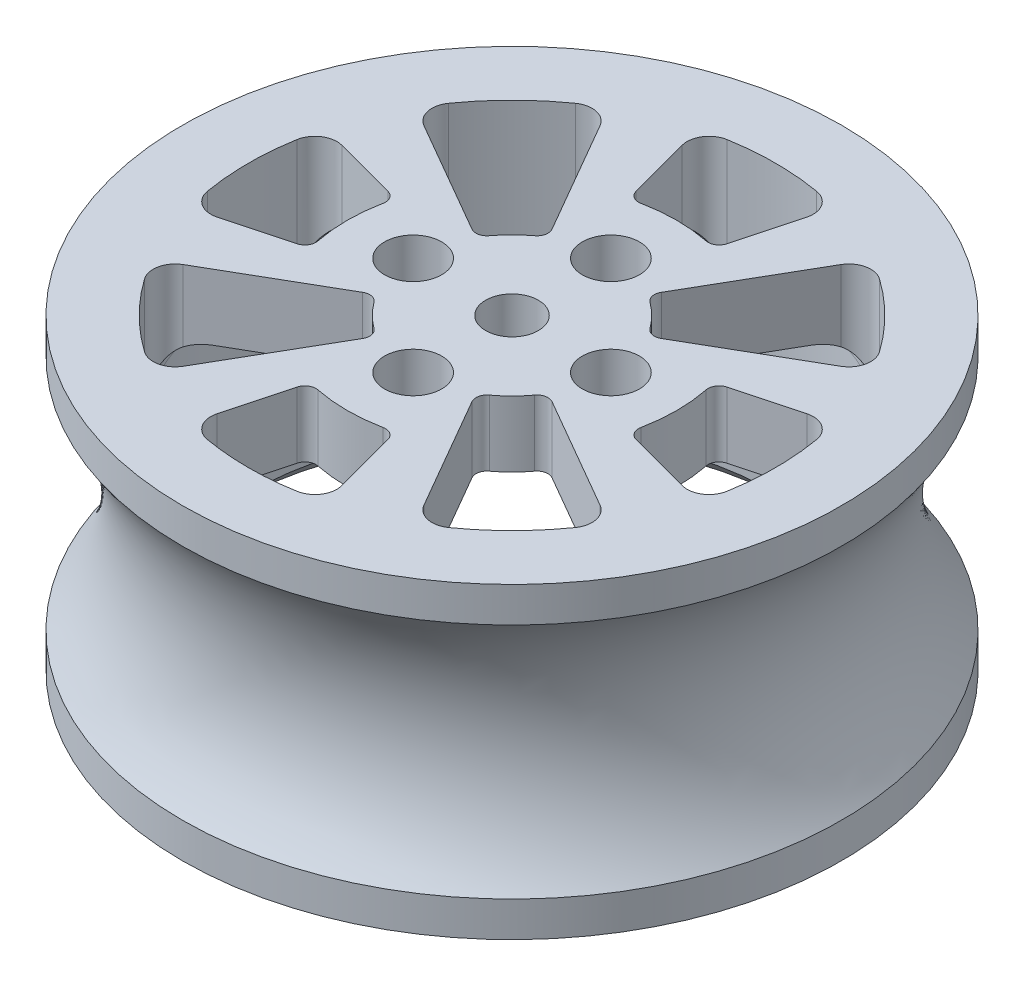
SolidWorks part; units mm, degrees
ref_plane "Front Plane" through (0, 0, 0) normal (0, 0, 1) x (1, 0, 0)
ref_plane "Top Plane" through (0, 0, 0) normal (0, 1, 0) x (1, 0, 0)
ref_plane "Right Plane" through (0, 0, 0) normal (1, 0, 0) x (0, 0, -1)
sketch "Sketch1" plane through (0, 0, 0) normal (0, 0, 1) x (1, 0, 0)
  line L0 (-0.1385, 3.875) -> (8.6615, 3.875)
  line L1 (11.8615, -0.125) -> (11.8615, 6.875) construction
  line L2 (13.6615, 6.875) -> (13.6615, 5.275)
  line L3 (-0.1385, 6.875) -> (-0.1385, 3.875)
  line L4 (10.6615, 1.875) -> (10.6615, -7.125)
  line L5 (-1.3385, 6.875) -> (-1.3385, -7.125) construction
  line L6 (13.6615, -5.525) -> (13.6615, -7.125)
  line L7 (13.6615, 6.875) -> (-0.1385, 6.875)
  line L10 (13.6615, -7.125) -> (10.6615, -7.125)
  arc A0 (13.6615, 5.275) -> (11.8615, -0.125) centre (20.8615, -0.125) ccw
  arc A1 (8.6615, 3.875) -> (10.6615, 1.875) centre (8.6615, 1.875) cw
  arc A3 (11.8615, -0.125) -> (13.6615, -5.525) centre (20.8615, -0.125) ccw
  dimension "D3" = 13.2
  dimension "D2" = 9
  dimension "D8" = 2
  dimension "D10" = 12
  dimension "D4" = 1.2
  dimension "D5" = 15
  dimension "D6" = 14
  dimension "D7" = 3
  dimension "D9" = 4
  dimension "D11" = 3.875
  dimension "D12" = 1.3385
revolve "Revolve1" add sketch "Sketch1" angle 360 about L5
hole_wizard "M2 Clearance Hole1" positions "Sketch3" profile "Sketch2" hole size "M2" standard "DIN" end condition up to next
sketch "Sketch3" plane through (0, 6.875, 0) normal (0, 1, 0) x (1, 0, 0)
  circle A4 centre (-1.3385, 0) radius 1.2 construction
  point P0 (-5.8385, 0)
  point P2 (-1.3385, 4.5)
  point P4 (3.1615, 0)
  point P6 (-1.3385, -4.5)
  dimension "D5" = 4.5
  dimension "D1" = 9
  dimension "D2" = 9
  dimension "D3" = 4.5
  dimension "D4" = 4.5
sketch "Sketch2" plane through (-5.8385, 6.875, 0) normal (1, 0, 0) x (0, 0, 1)
  line L0 (0, 0) -> (0, 3)
  line L1 (0, 3) -> (1.3, 3)
  line L2 (1.3, 3) -> (1.3, 0)
  line L5 (1.3, 0) -> (0, 0)
  line L11 (0, -6.35) -> (0, 107.95) construction
  dimension "Thru Hole Dia." = 2.6
  dimension "Thru Hole Depth" = 3
sketch "Sketch5" plane through (0, 6.875, 0) normal (0, 1, 0) x (1, 0, 0)
  line L0 (1.149, -4.3084) -> (4.1388, -9.4868)
  line L1 (2.97, -2.4875) -> (8.1484, -5.4772)
  line L2 (-1.3385, 0) -> (-9.8237, 8.4853) construction
  line L3 (-1.3385, 0) -> (-9.8237, -8.4853) construction
  line L4 (-5.6469, -2.4875) -> (-10.8253, -5.4772)
  line L5 (-3.8259, -4.3084) -> (-6.8157, -9.4868)
  line L6 (-3.8259, 4.3084) -> (-6.8157, 9.4868)
  line L7 (-5.6469, 2.4875) -> (-10.8253, 5.4772)
  line L8 (-1.3385, 12) -> (-1.3385, -12) construction
  line L9 (2.97, 2.4875) -> (8.1484, 5.4772)
  line L10 (1.149, 4.3084) -> (4.1388, 9.4868)
  line L11 (-4.1737, -10.5812) -> (-3.405, -7.7123)
  line L12 (-9.0508, -2.0665) -> (-11.9197, -2.8352)
  line L13 (-11.9197, 2.8352) -> (-9.0508, 2.0665)
  line L14 (-4.1737, 10.5812) -> (-3.405, 7.7123)
  line L15 (-13.3385, 0) -> (10.6615, 0) construction
  line L16 (-1.3385, 0) -> (-5.6469, 2.4875) construction
  line L17 (-3.8259, 4.3084) -> (-1.3385, 0) construction
  line L18 (-8.5829, -1.9411) -> (-1.3385, 0) construction
  line L19 (-1.3385, 0) -> (-8.5829, 1.9411) construction
  line L20 (-5.6469, -2.4875) -> (-1.3385, 0) construction
  line L21 (-1.3385, 0) -> (-3.8259, -4.3084) construction
  line L22 (-3.2796, -7.2444) -> (-1.3385, 0) construction
  line L23 (-1.3385, 0) -> (-3.2796, 7.2444) construction
  line L24 (1.4968, -10.5812) -> (0.728, -7.7123)
  line L25 (6.3738, -2.0665) -> (9.2427, -2.8352)
  line L26 (9.2427, 2.8352) -> (6.3738, 2.0665)
  line L27 (1.4968, 10.5812) -> (0.728, 7.7123)
  arc A0 (-8.2584, 9.8038) -> (-11.1423, 6.9199) centre (-1.3385, 0) ccw
  arc A1 (0.7008, 11.8255) -> (-3.3777, 11.8255) centre (-1.3385, 0) ccw
  arc A2 (-3.9669, 3.6526) -> (-4.991, 2.6284) centre (-1.3385, 0) ccw
  arc A3 (-11.1423, -6.9199) -> (-8.2584, -9.8038) centre (-1.3385, 0) ccw
  arc A4 (-4.991, -2.6284) -> (-3.9669, -3.6526) centre (-1.3385, 0) ccw
  arc A5 (8.4654, -6.9199) -> (5.5814, -9.8038) centre (-1.3385, 0) cw
  arc A6 (2.3141, -2.6284) -> (1.29, -3.6526) centre (-1.3385, 0) cw
  arc A7 (1.29, 3.6526) -> (2.3141, 2.6284) centre (-1.3385, 0) cw
  arc A8 (5.5814, 9.8038) -> (8.4654, 6.9199) centre (-1.3385, 0) cw
  arc A9 (1.29, 3.6526) -> (1.149, 4.3084) centre (1.582, 4.0584) cw
  arc A10 (2.97, 2.4875) -> (2.3141, 2.6284) centre (2.72, 2.9205) cw
  arc A11 (2.97, -2.4875) -> (2.3141, -2.6284) centre (2.72, -2.9205) ccw
  arc A12 (1.149, -4.3084) -> (1.29, -3.6526) centre (1.582, -4.0584) cw
  arc A13 (-3.9669, -3.6526) -> (-3.8259, -4.3084) centre (-4.2589, -4.0584) cw
  arc A14 (-5.6469, -2.4875) -> (-4.991, -2.6284) centre (-5.3969, -2.9205) cw
  arc A15 (-5.6469, 2.4875) -> (-4.991, 2.6284) centre (-5.3969, 2.9205) ccw
  arc A16 (-3.8259, 4.3084) -> (-3.9669, 3.6526) centre (-4.2589, 4.0584) cw
  arc A17 (5.5814, 9.8038) -> (4.1388, 9.4868) centre (5.0048, 8.9868) ccw
  arc A18 (8.1484, 5.4772) -> (8.4654, 6.9199) centre (7.6484, 6.3433) ccw
  arc A19 (8.4654, -6.9199) -> (8.1484, -5.4772) centre (7.6484, -6.3433) ccw
  arc A20 (4.1388, -9.4868) -> (5.5814, -9.8038) centre (5.0048, -8.9868) ccw
  arc A21 (-6.8157, -9.4868) -> (-8.2584, -9.8038) centre (-7.6817, -8.9868) cw
  arc A22 (-11.1423, -6.9199) -> (-10.8253, -5.4772) centre (-10.3253, -6.3433) cw
  arc A23 (-10.8253, 5.4772) -> (-11.1423, 6.9199) centre (-10.3253, 6.3433) cw
  arc A24 (-6.8157, 9.4868) -> (-8.2584, 9.8038) centre (-7.6817, 8.9868) ccw
  arc A25 (-13.1639, 2.0392) -> (-13.1639, -2.0392) centre (-1.3385, 0) ccw
  arc A26 (0.7008, -11.8255) -> (-3.3777, -11.8255) centre (-1.3385, 0) cw
  arc A27 (0.1461, 7.3516) -> (-2.823, 7.3516) centre (-1.3385, 0) ccw
  arc A28 (-8.6901, 1.4846) -> (-8.6901, -1.4846) centre (-1.3385, 0) ccw
  arc A29 (-2.823, -7.3516) -> (0.1461, -7.3516) centre (-1.3385, 0) ccw
  arc A30 (-3.3777, 11.8255) -> (-4.1737, 10.5812) centre (-3.2078, 10.84) ccw
  arc A31 (-13.1639, 2.0392) -> (-11.9197, 2.8352) centre (-12.1785, 1.8693) cw
  arc A32 (-13.1639, -2.0392) -> (-11.9197, -2.8352) centre (-12.1785, -1.8693) ccw
  arc A33 (-3.3777, -11.8255) -> (-4.1737, -10.5812) centre (-3.2078, -10.84) cw
  arc A34 (-9.0508, 2.0665) -> (-8.6901, 1.4846) centre (-9.1802, 1.5835) cw
  arc A35 (-3.405, 7.7123) -> (-2.823, 7.3516) centre (-2.922, 7.8417) ccw
  arc A36 (-3.405, -7.7123) -> (-2.823, -7.3516) centre (-2.922, -7.8417) cw
  arc A37 (-9.0508, -2.0665) -> (-8.6901, -1.4846) centre (-9.1802, -1.5835) ccw
  arc A38 (0.7008, -11.8255) -> (1.4968, -10.5812) centre (0.5308, -10.84) ccw
  arc A39 (0.728, -7.7123) -> (0.1461, -7.3516) centre (0.2451, -7.8417) ccw
  arc A40 (10.487, 2.0392) -> (9.2427, 2.8352) centre (9.5015, 1.8693) ccw
  arc A41 (10.487, 2.0392) -> (10.487, -2.0392) centre (-1.3385, 0) cw
  arc A42 (10.487, -2.0392) -> (9.2427, -2.8352) centre (9.5015, -1.8693) cw
  arc A43 (6.3738, -2.0665) -> (6.0131, -1.4846) centre (6.5032, -1.5835) cw
  arc A44 (6.0131, 1.4846) -> (6.0131, -1.4846) centre (-1.3385, 0) cw
  arc A45 (6.3738, 2.0665) -> (6.0131, 1.4846) centre (6.5032, 1.5835) ccw
  arc A46 (0.728, 7.7123) -> (0.1461, 7.3516) centre (0.2451, 7.8417) cw
  arc A47 (0.7008, 11.8255) -> (1.4968, 10.5812) centre (0.5308, 10.84) cw
  point P24 (0.9115, 3.8971)
  point P27 (2.5586, 2.25)
  point P30 (2.5586, -2.25)
  point P33 (0.9115, -3.8971)
  point P36 (-3.5885, -3.8971)
  point P39 (-5.2356, -2.25)
  point P42 (-5.2356, 2.25)
  point P45 (-3.5885, 3.8971)
  point P48 (4.6615, 10.3923)
  point P51 (9.0538, 6)
  point P54 (9.0538, -6)
  point P57 (4.6615, -10.3923)
  point P60 (-7.3385, -10.3923)
  point P63 (-11.7308, -6)
  point P66 (-11.7308, 6)
  point P69 (-7.3385, 10.3923)
  dimension "D1" = 24
  dimension "D2" = 9
  dimension "D9" = 0.5
  dimension "D10" = 1
  dimension "D11" = 15
  dimension "D17" = 1
  dimension "D18" = 1
  dimension "D19" = 0.5
  dimension "D20" = 0.5
  dimension "D3" = 15
  dimension "D4" = 45
  dimension "D5" = 15
  dimension "D6" = 45
  dimension "D7" = 15
  dimension "D8" = 15
  dimension "D12" = 15
  dimension "D13" = 15
  dimension "D14" = 15
  dimension "D15" = 15
  dimension "D16" = 90
extrude "Cut-Extrude1" cut sketch "Sketch5" against normal up to next
chamfer "Chamfer1" distance 1 angle 45 1 edges at (-1.3385, -7.125, 12)
